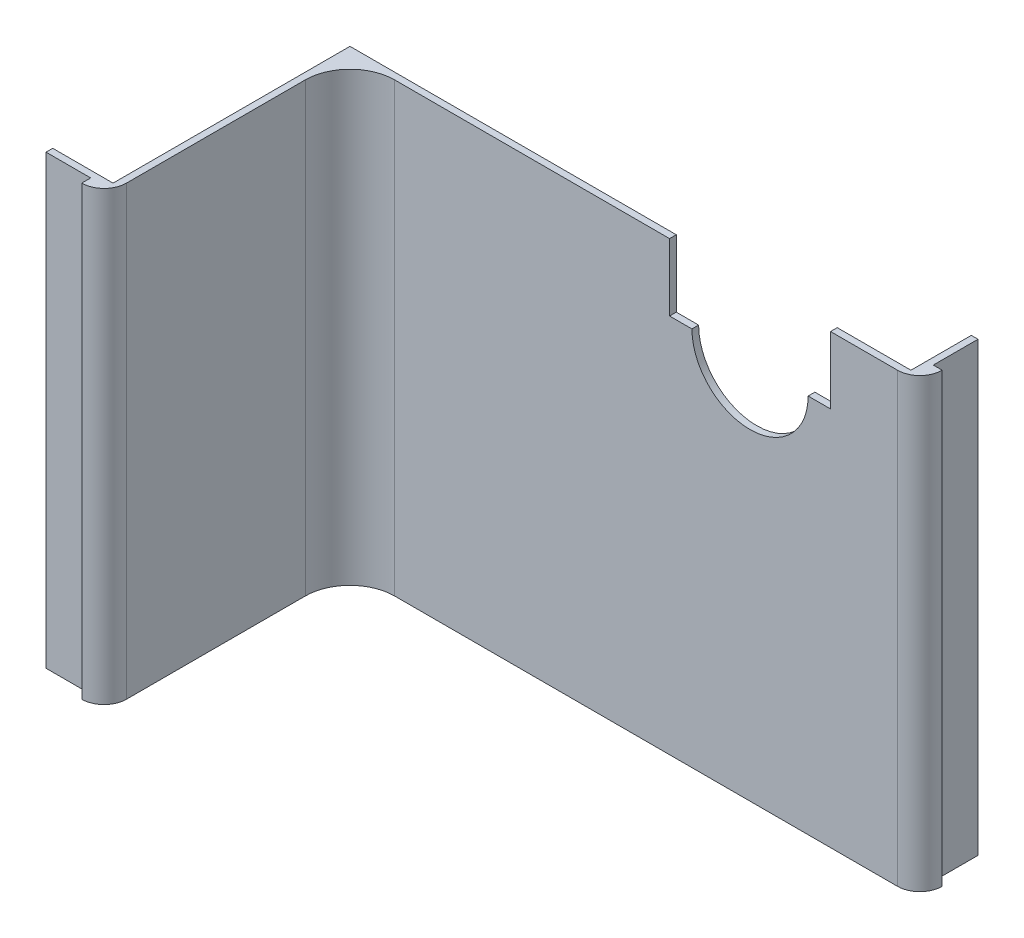
SolidWorks part; units mm, degrees
material "ABS"
ref_plane "Спереди" through (0, 0, 0) normal (0, 0, 1) x (1, 0, 0)
ref_plane "Сверху" through (0, 0, 0) normal (0, 1, 0) x (1, 0, 0)
ref_plane "Справа" through (0, 0, 0) normal (1, 0, 0) x (0, 0, -1)
sketch "Эскиз1" plane through (0, 0, 0) normal (0, 1, 0) x (1, 0, 0)
  line L0 (0, 0) -> (-112.5, 0)
  line L1 (-122.5, -10) -> (-122.5, -50)
  line L2 (-127.5, -55) -> (-127.5, -53)
  line L3 (-127.5, -53) -> (-137.5, -53)
  line L4 (5, 5) -> (3, 5)
  line L5 (3, 5) -> (3, 15)
  line L6 (3, 15) -> (1.5, 15)
  line L7 (0, 0) -> (0, 1.5) construction
  line L8 (1.5, 15) -> (1.5, 1.5)
  line L9 (-122.5, -50) -> (-124, -50) construction
  line L10 (-137.5, -53) -> (-137.5, -51.5)
  line L11 (-137.5, -51.5) -> (-124, -51.5)
  line L12 (-124, -51.5) -> (-124, 1.5)
  line L13 (-124, 1.5) -> (1.5, 1.5)
  arc A0 (-112.5, 0) -> (-122.5, -10) centre (-112.5, -10) ccw
  arc A1 (-122.5, -50) -> (-127.5, -55) centre (-127.5, -50) cw
  arc A2 (0, 0) -> (5, 5) centre (0, 5) ccw
  dimension "D1" = 112.5
  dimension "D2" = 5
  dimension "D6" = 10
  dimension "D9" = 5
  dimension "D3" = 2
  dimension "D4" = 1.5
  dimension "D5" = 1.5
  dimension "D7" = 1.5
  dimension "D8" = 40
  dimension "D10" = 2
  dimension "D11" = 1.5
  dimension "D12" = 10
  dimension "D13" = 10
extrude "Бобышка-Вытянуть1" add sketch "Эскиз1" along normal blind 100
sketch "Эскиз4" plane through (0, 0, 0) normal (0, 0, 1) x (1, 0, 0)
  line L8 (-51, 85) -> (-15, 85) construction
  line L11 (5, 50) -> (-55.9199, 50) construction
  line L12 (5, 100) -> (-15, 100) construction
  line L13 (-15, 85) -> (-20, 85)
  line L14 (-15, 100) -> (-15, 85)
  line L15 (-51, 85) -> (-46, 85)
  line L16 (-51, 100) -> (-51, 85)
  line L17 (-15, 100) -> (-51, 100)
  arc A1 (-20, 85) -> (-46, 85) centre (-33, 85) cw
extrude "Вырез-Вытянуть1" cut sketch "Эскиз4" against normal through all
